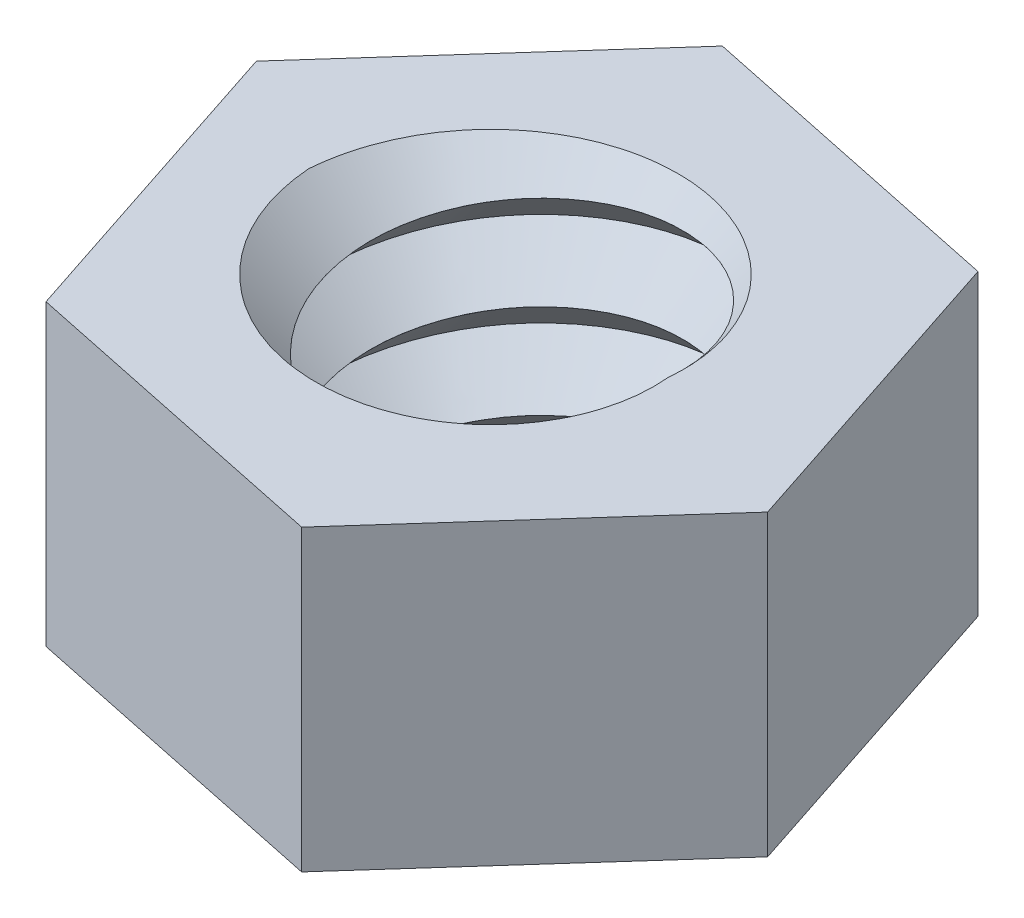
SolidWorks part; units mm, degrees
ref_plane "Front Plane" through (0, 0, 0) normal (0, 0, 1) x (1, 0, 0)
ref_plane "Top Plane" through (0, 0, 0) normal (0, 1, 0) x (1, 0, 0)
ref_plane "Right Plane" through (0, 0, 0) normal (1, 0, 0) x (0, 0, -1)
sketch "Sketch1" plane through (0, 0, 0) normal (0, 1, 0) x (1, 0, 0)
  line L0 (-90.4875, 0) -> (0, 0) construction
  line L14 (7.0152, 7.8492) -> (-3.29, 10)
  line L15 (-3.29, 10) -> (-10.3053, 2.1508)
  line L16 (-10.3053, 2.1508) -> (-7.0152, -7.8492)
  line L17 (-7.0152, -7.8492) -> (3.29, -10)
  line L18 (3.29, -10) -> (10.3053, -2.1508)
  line L19 (10.3053, -2.1508) -> (7.0152, 7.8492)
  circle A3 centre (0, 0) radius 5
  circle A6 centre (0, 0) radius 9.1169 construction
  point P0 (0, 0)
  dimension "D11" = 10
extrude "Boss-Extrude1" add sketch "Sketch1" along normal blind 9.525 contours A3 region at (8.3874, 0, -2.7595)
sketch "Sketch5" plane through (0, 9.525, 0) normal (0, 1, 0) x (1, 0, 0)
  circle A0 centre (0, 0) radius 5 construction
  circle A1 centre (0, 0) radius 5
curve "Helix/Spiral2" pitch 3 height 15 radius 5 left hand yes centre (0, 9.525, 0) axis (0, -1, 0) start towards (0, 0, 1)
sketch "Sketch6" plane through (0, 9.525, 0) normal (0, 1, 0) x (1, 0, 0)
  circle A2 centre (0, 0) radius 5 construction
  circle A3 centre (0, 0) radius 5
  point P3 (0, 0)
sketch "Sketch7" plane through (0, 0, 0) normal (0, 0, 1) x (1, 0, 0)
  line L0 (0, 9.525) -> (5, 9.525) construction
  line L5 (5, 9.525) -> (5, 12.524)
  line L8 (5, 12.524) -> (6.4995, 11.0245)
  line L9 (6.4995, 11.0245) -> (5, 9.525)
  line L10 (5, 11.0245) -> (6.4995, 11.0245) construction
  spline S0 degree 3 poles (999.9275, -2.4099) (-68.6097, 12.8568) (-12.4556, 10.9622) (3.6271, 9.15) (4.7398, 8.9625) (5.1301, 8.775) (4.7397, 8.5875) (3.6276, 8.4) (1.4085, 8.15) (-1.4084, 7.9) (-3.6276, 7.65) (-4.7397, 7.4625) (-5.1302, 7.275) (-4.7397, 7.0875) (-3.6276, 6.9) (-1.4084, 6.65) (1.4084, 6.4) (3.6276, 6.15) (4.7397, 5.9625) (5.1302, 5.775) (4.7397, 5.5875) (3.6276, 5.4) (1.4084, 5.15) (-1.4084, 4.9) (-3.6276, 4.65) (-4.7397, 4.4625) (-5.1302, 4.275) (-4.7397, 4.0875) (-3.6276, 3.9) (-1.4084, 3.65) (1.4084, 3.4) (3.6276, 3.15) (4.7397, 2.9625) (5.1302, 2.775) (4.7397, 2.5875) (3.6276, 2.4) (1.4084, 2.15) (-1.4084, 1.9) (-3.6276, 1.65) (-4.7397, 1.4625) (-5.1302, 1.275) (-4.7397, 1.0875) (-3.6276, 0.9) (-1.4084, 0.65) (1.4084, 0.4) (3.6276, 0.15) (4.7397, -0.0375) (5.1302, -0.225) (4.7397, -0.4125) (3.6276, -0.6) (1.4084, -0.85) (-1.4084, -1.1) (-3.6276, -1.35) (-4.7397, -1.5375) (-5.1302, -1.725) (-4.7397, -1.9125) (-3.6276, -2.1) (-1.4084, -2.35) (1.4084, -2.6) (3.6276, -2.85) (4.7397, -3.0375) (5.1302, -3.225) (4.7397, -3.4125) (3.6276, -3.6) (1.4084, -3.85) (-1.4085, -4.1) (-3.6276, -4.35) (-4.7397, -4.5375) (-5.1301, -4.725) (-4.7398, -4.9125) (-3.6271, -5.1) (12.4553, -6.9122) (68.6076, -8.8067) (-999.8639, 6.459) knots -0.325388 -0.325388 -0.325388 -0.325388 0.0125 0.025 0.0375 0.05 0.0625 0.075 0.0875 0.1125 0.125 0.1375 0.15 0.1625 0.175 0.1875 0.2125 0.225 0.2375 0.25 0.2625 0.275 0.2875 0.3125 0.325 0.3375 0.35 0.3625 0.375 0.3875 0.4125 0.425 0.4375 0.45 0.4625 0.475 0.4875 0.5125 0.525 0.5375 0.55 0.5625 0.575 0.5875 0.6125 0.625 0.6375 0.65 0.6625 0.675 0.6875 0.7125 0.725 0.7375 0.75 0.7625 0.775 0.7875 0.8125 0.825 0.8375 0.85 0.8625 0.875 0.8875 0.9125 0.925 0.9375 0.95 0.9625 0.975 0.9875 1.325381 1.325381 1.325381 1.325381 only from (0, 9.525) to (0, -5.475) construction
  spline S1 degree 3 poles (0, 9.525) (0.6503, 9.4629) (1.9651, 9.3373) (3.6271, 9.15) (4.7398, 8.9625) (5.1301, 8.775) (4.7397, 8.5875) (3.6276, 8.4) (1.4085, 8.15) (-1.4084, 7.9) (-3.6276, 7.65) (-4.7397, 7.4625) (-5.1302, 7.275) (-4.7397, 7.0875) (-3.6276, 6.9) (-1.4084, 6.65) (1.4084, 6.4) (3.6276, 6.15) (4.7397, 5.9625) (5.1302, 5.775) (4.7397, 5.5875) (3.6276, 5.4) (1.4084, 5.15) (-1.4084, 4.9) (-3.6276, 4.65) (-4.7397, 4.4625) (-5.1302, 4.275) (-4.7397, 4.0875) (-3.6276, 3.9) (-1.4084, 3.65) (1.4084, 3.4) (3.6276, 3.15) (4.7397, 2.9625) (5.1302, 2.775) (4.7397, 2.5875) (3.6276, 2.4) (1.4084, 2.15) (-1.4084, 1.9) (-3.6276, 1.65) (-4.7397, 1.4625) (-5.1302, 1.275) (-4.7397, 1.0875) (-3.6276, 0.9) (-1.4084, 0.65) (1.4084, 0.4) (3.6276, 0.15) (4.7397, -0.0375) (5.1302, -0.225) (4.7397, -0.4125) (3.6276, -0.6) (1.4084, -0.85) (-1.4084, -1.1) (-3.6276, -1.35) (-4.7397, -1.5375) (-5.1302, -1.725) (-4.7397, -1.9125) (-3.6276, -2.1) (-1.4084, -2.35) (1.4084, -2.6) (3.6276, -2.85) (4.7397, -3.0375) (5.1302, -3.225) (4.7397, -3.4125) (3.6276, -3.6) (1.4084, -3.85) (-1.4085, -4.1) (-3.6276, -4.35) (-4.7397, -4.5375) (-5.1301, -4.725) (-4.7398, -4.9125) (-3.6271, -5.1) (-1.9651, -5.2873) (-0.6503, -5.4129) (0, -5.475) knots 0 0 0 0 0.0125 0.025 0.0375 0.05 0.0625 0.075 0.0875 0.1125 0.125 0.1375 0.15 0.1625 0.175 0.1875 0.2125 0.225 0.2375 0.25 0.2625 0.275 0.2875 0.3125 0.325 0.3375 0.35 0.3625 0.375 0.3875 0.4125 0.425 0.4375 0.45 0.4625 0.475 0.4875 0.5125 0.525 0.5375 0.55 0.5625 0.575 0.5875 0.6125 0.625 0.6375 0.65 0.6625 0.675 0.6875 0.7125 0.725 0.7375 0.75 0.7625 0.775 0.7875 0.8125 0.825 0.8375 0.85 0.8625 0.875 0.8875 0.9125 0.925 0.9375 0.95 0.9625 0.975 0.9875 1 1 1 1 construction
  dimension "D1" = 2.999
sweep "Cut-Sweep1" cut profiles "Sketch7" path "Helix/Spiral2" align with end faces yes
